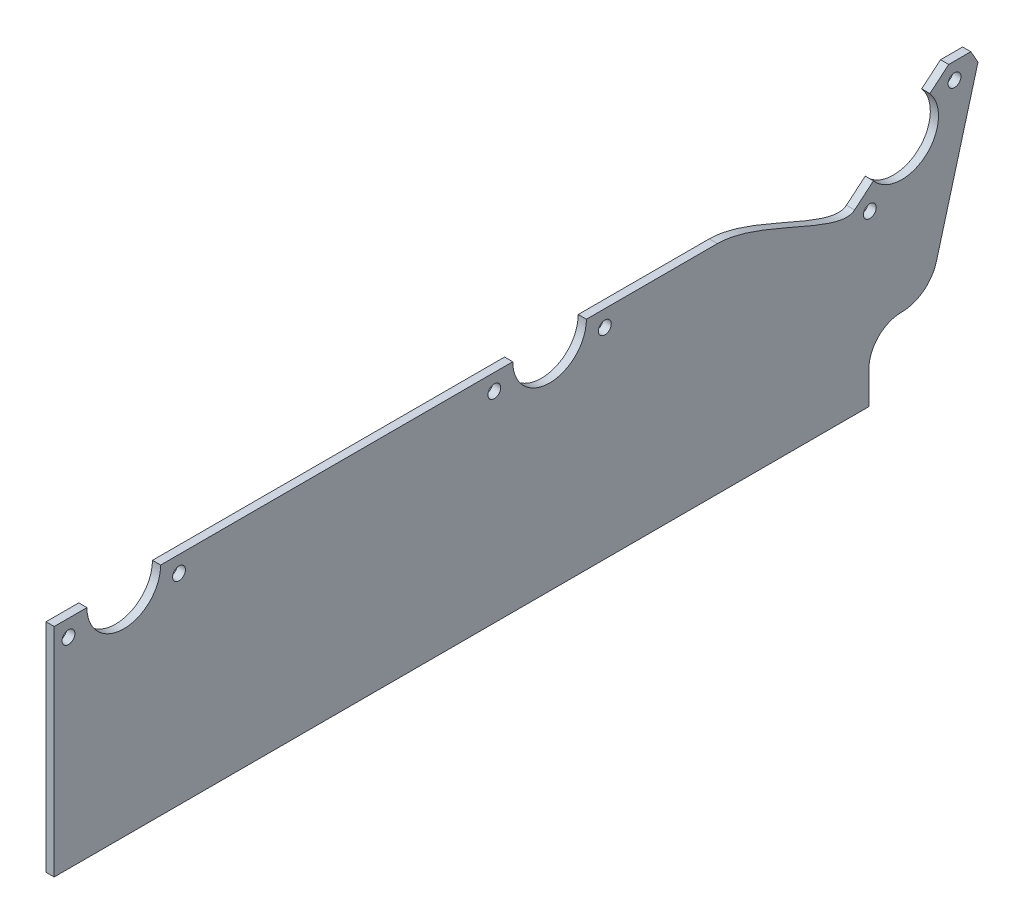
SolidWorks part; units mm, degrees
material "6061 Alloy"
ref_plane "Front Plane" through (0, 0, 0) normal (0, 0, 1) x (1, 0, 0)
ref_plane "Top Plane" through (0, 0, 0) normal (0, 1, 0) x (1, 0, 0)
ref_plane "Right Plane" through (0, 0, 0) normal (1, 0, 0) x (0, 0, -1)
sketch "Sketch1" plane through (0, 0, 0) normal (1, 0, 0) x (0, 0, -1)
  line L0 (-12.7, -12.7) -> (-328.6125, -12.7)
  line L1 (-328.6125, -12.7) -> (-328.6125, 71.4375)
  line L2 (-328.6125, 71.4375) -> (-315.9125, 71.4375)
  line L3 (-287.3375, 71.4375) -> (-150.8125, 71.4375)
  line L5 (10.9449, 80.6213) -> (18.2432, 86.7453)
  line L7 (-328.6125, 12.7) -> (13.4735, 12.7) construction
  line L8 (-12.7, -12.7) -> (-12.7, 0)
  line L9 (0, 12.4079) -> (0, 12.7) construction
  line L10 (13.4735, 22.9788) -> (30.9432, 86.7453)
  line L12 (-10.9449, 62.2537) -> (10.9449, 80.6213) construction
  line L13 (18.2432, 86.7453) -> (30.9432, 86.7453)
  line L14 (-122.2375, 71.4375) -> (-71.4375, 71.4375)
  line L15 (-10.9449, 62.2537) -> (-18.2432, 56.1297)
  line L16 (-328.6125, 15.875) -> (13.4735, 15.875) construction
  line L18 (0, 71.4375) -> (-136.525, 71.4375) construction
  arc A3 (0, 12.7) -> (13.4735, 22.9788) centre (0, 26.67) ccw
  arc A4 (0, 12.7) -> (-12.7, 0) centre (0, 0) ccw
  circle A5 centre (0, 0) radius 12.4079 construction
  arc A6 (-315.9125, 71.4375) -> (-287.3375, 71.4375) centre (-301.625, 71.4375) ccw
  arc A7 (-150.8125, 71.4375) -> (-122.2375, 71.4375) centre (-136.525, 71.4375) ccw
  arc A8 (-10.9449, 62.2537) -> (10.9449, 80.6213) centre (0, 71.4375) ccw
  spline S0 degree 3 poles (-18.2432, 56.1297) (-24.729, 50.6874) (-54.5042, 71.4375) (-71.4375, 71.4375) knots 0 0 0 0 1 1 1 1
  point P4 (-170.6562, -12.7)
  point P25 (0, 0)
  dimension "D1" = 25.4
  dimension "D3" = 12.7
  dimension "D5" = 28.575
  dimension "D6" = 41.275
  dimension "D7" = 13.97
  dimension "D8" = 12.7
  dimension "D10" = 24.8158
  dimension "D13" = 9.5273
  dimension "D14" = 140
  dimension "D15" = 50.8
  dimension "D16" = 50.8
  dimension "D17" = 25.4
  dimension "D2" = 0
  dimension "D4" = 12.7
  dimension "D9" = 12.7
  dimension "D11" = 301.625
  dimension "D12" = 301.625
  dimension "D18" = 3.175
extrude "Boss-Extrude1" add sketch "Sketch1" along normal blind 3.175
hole_wizard "#10 Clearance Hole1" positions "Sketch2" profile "Sketch3" hole size "#10" standard "ANSI Inch" end condition through all
sketch "Sketch2" plane through (3.175, 0, 0) normal (1, 0, 0) x (0, 0, -1)
  line L0 (-323.0562, 65.0875) -> (-280.1937, 65.0875) construction
  line L2 (-157.9562, 65.0875) -> (-115.0938, 65.0875) construction
  line L4 (-12.3356, 52.7974) -> (20.499, 80.3489) construction
  line L6 (-315.9125, 71.4375) -> (-328.6125, 71.4375) construction
  line L7 (-301.625, 65.0875) -> (-301.625, 71.4375) construction
  line L9 (-136.525, 71.4375) -> (-136.525, 65.0875) construction
  line L11 (0, 71.4375) -> (4.0817, 66.5731) construction
  line L14 (18.2432, 86.7453) -> (10.9449, 80.6213) construction
  line L15 (18.2432, 86.7453) -> (10.9449, 80.6213) construction
  point P0 (-323.0562, 65.0875)
  point P2 (-280.1937, 65.0875)
  point P4 (-157.9562, 65.0875)
  point P6 (-115.0938, 65.0875)
  point P8 (-12.3356, 52.7974)
  point P10 (20.499, 80.3489)
  dimension "D1" = 42.8625
  dimension "D2" = 6.35
  dimension "D3" = 6.35
sketch "Sketch3" plane through (3.175, 65.0875, 323.0562) normal (0, 1, 0) x (0, 0, -1)
  line L0 (0, 0) -> (0, 3.175)
  line L1 (0, 3.175) -> (2.4892, 3.175)
  line L2 (2.4892, 3.175) -> (2.4892, 0)
  line L5 (2.4892, 0) -> (0, 0)
  line L11 (0, -6.35) -> (0, 107.95) construction
  dimension "Thru Hole Dia." = 4.9784
  dimension "Thru Hole Depth" = 3.175
chamfer "Chamfer1" distance 5.08 angle 45 1 edges at (1.5875, 86.7453, -30.9432) first distance on face at (1.5875, 54.862, -22.2083)
